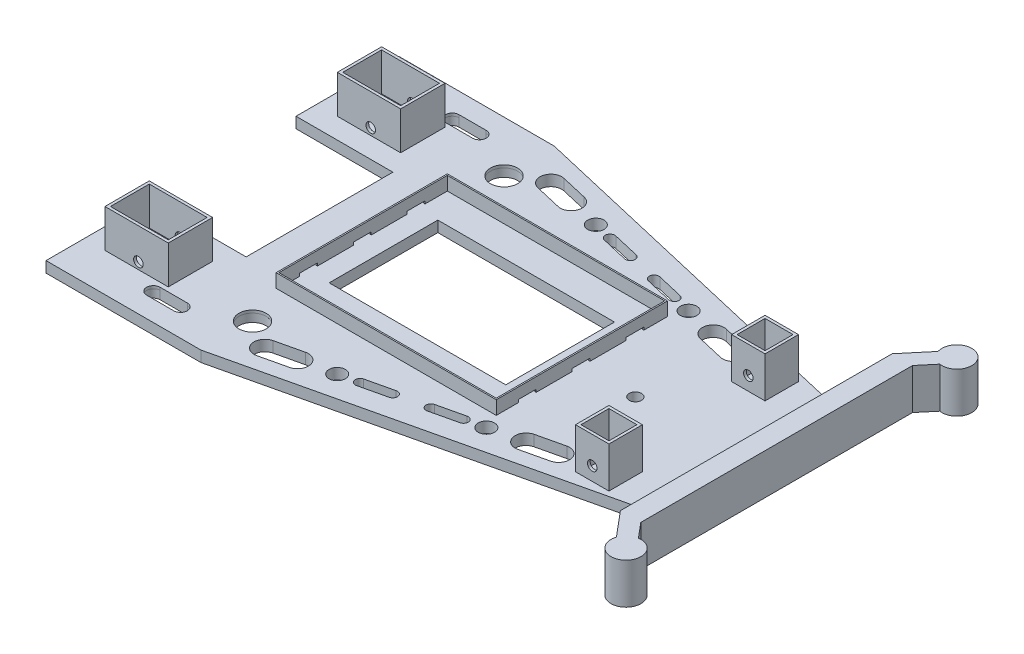
SolidWorks part; units mm, degrees
other "Markup1"
sketch "Sketch21" plane through (-125.0066, 16, 66.3806) normal (-0.0295, 0.9995, 0.0098) x (0.1853, -0.0042, 0.9827)
ref_plane "Front Plane" through (0, 0, 0) normal (0, 0, 1) x (1, 0, 0)
ref_plane "Top Plane" through (0, 0, 0) normal (0, 1, 0) x (1, 0, 0)
ref_plane "Right Plane" through (0, 0, 0) normal (1, 0, 0) x (0, 0, -1)
sketch "Sketch1" plane through (0, 0, 0) normal (0, 1, 0) x (1, 0, 0)
  line L0 (-125, -100) -> (-125, -65)
  line L1 (-125, -100) -> (125, -100)
  line L2 (-125, -100) -> (-125, 100)
  line L3 (-125, 100) -> (125, 100)
  line L4 (125, -100) -> (125, 100)
  line L5 (-125, -100) -> (125, 100) construction
  line L6 (-125, 100) -> (125, -100) construction
  line L7 (-125, -65) -> (-55, -65)
  line L8 (-55, -65) -> (-55, -100)
  line L9 (-55, -100) -> (-125, -100)
  line L10 (43.75, -65) -> (125, 0)
  line L11 (-55, 100) -> (-125, 100)
  line L12 (-55, 65) -> (-55, 100)
  line L13 (-125, 65) -> (-55, 65)
  line L14 (-125, 100) -> (-125, 65)
  line L15 (125, 0) -> (43.75, 65)
  line L16 (-55, -65) -> (43.75, -65)
  line L17 (-55, 65) -> (43.75, 65)
  line L18 (-131.3472, 0) -> (-131.3472, 27)
  line L19 (-131.3472, 27) -> (-76.3472, 27)
  line L20 (-76.3472, 27) -> (-76.3472, -27)
  line L21 (-76.3472, -27) -> (-131.5339, -27)
  line L22 (-131.3472, 0) -> (-131.3472, -27)
  line L29 (-82.5, 55) -> (-72.5, 55) construction
  line L31 (-82.5, -55) -> (-72.5, -55) construction
  line L32 (-82.5, -52.5) -> (-72.5, -52.5)
  line L33 (-82.5, -57.5) -> (-72.5, -57.5)
  line L34 (-82.5, 52.5) -> (-72.5, 52.5)
  line L35 (-82.5, 57.5) -> (-72.5, 57.5)
  arc A4 (-82.5, -52.5) -> (-82.5, -57.5) centre (-82.5, -55) ccw
  arc A5 (-72.5, -57.5) -> (-72.5, -52.5) centre (-72.5, -55) ccw
  circle A6 centre (-54.7227, -46.2677) radius 5
  circle A7 centre (-54.7227, 46.2677) radius 5
  arc A8 (-82.5, 52.5) -> (-82.5, 57.5) centre (-82.5, 55) cw
  arc A9 (-72.5, 57.5) -> (-72.5, 52.5) centre (-72.5, 55) cw
  point P0 (0, 0)
  point P44 (-77.5, -55)
  point P53 (-77.5, 55)
  dimension "D3" = 10
  dimension "D4" = 2.5
  dimension "D1" = 125
  dimension "D2" = 100
  dimension "D5" = 43.75
  dimension "D6" = 55
  dimension "D7" = 72.5
  dimension "D8" = 76.3472
  dimension "D9" = 77.5
  dimension "D10" = 27
  dimension "D11" = 131.3472
  dimension "D12" = 131.5339
  dimension "D13" = 46.2677
  dimension "D14" = 55
  dimension "D15" = 65
  dimension "D17" = 55
extrude "Boss-Extrude1" add sketch "Sketch1" along normal blind 1 contours L17 L13 L2 L7 L16 L10 L15 region at (-9.6002, 0, 0)
sketch "Sketch2" plane through (0, 0, 0) normal (0, 1, 0) x (1, 0, 0)
  line L1 (125, 0) -> (43.75, 65) construction
  line L2 (84.375, 32.5) -> (84.375, -32.5)
  line L3 (43.75, -65) -> (125, 0) construction
  line L4 (84.375, -32.5) -> (125, 0)
  line L5 (125, 0) -> (84.375, 32.5)
extrude "Cut-Extrude2" cut sketch "Sketch2" along normal through all both and the other way through all
sketch "Sketch3" plane through (0, 0, 0) normal (0, 1, 0) x (1, 0, 0)
  line L0 (84.375, -32.5) -> (-55, -65)
  line L1 (43.75, -65) -> (125, 0) construction
  line L2 (84.375, 32.5) -> (-55, 65)
  line L3 (125, 0) -> (43.75, 65) construction
  line L4 (-55, 65) -> (84.375, 65)
  line L5 (84.375, 65) -> (84.375, 32.5)
  line L6 (-55, -65) -> (84.375, -65)
  line L7 (84.375, -65) -> (84.375, -32.5)
extrude "Cut-Extrude4" cut sketch "Sketch3" along normal blind 1
sketch "Sketch8" plane through (0, 0, 0) normal (0, 1, 0) x (1, 0, 0)
  line L0 (-8.25, 0) -> (8.25, 0) construction
  line L2 (-103.4, 49.9) -> (-103.4, 35.6)
  line L3 (-103.4, 35.6) -> (-82.1, 35.6)
  line L5 (-103.4, 49.9) -> (-82.1, 35.6) construction
  line L6 (-103.4, 35.6) -> (-92.75, 42.75) construction
  line L7 (-103.4, -35.6) -> (-82.1, -49.9) construction
  line L8 (-103.4, -49.9) -> (-82.1, -35.6) construction
  line L9 (-82.1, -49.9) -> (-82.1, -35.6)
  line L10 (-103.4, -35.6) -> (-82.1, -35.6)
  line L11 (-103.4, -49.9) -> (-103.4, -35.6)
  line L12 (-103.4, -49.9) -> (-82.1, -49.9)
  line L13 (-92.75, 42.75) -> (-82.1, 49.9) construction
  line L15 (-103.4, 49.9) -> (-82.1, 49.9)
  line L16 (-82.1, 49.9) -> (-82.1, 35.6)
  point P4 (-98.075, 39.175)
  point P11 (-92.75, -42.75)
  point P12 (-99.75, 49.9)
  point P13 (-89.1, 49.9)
  dimension "D1" = 82.1
  dimension "D2" = 92.75
  dimension "D3" = 35.6
  dimension "D4" = 99.75
ref_plane "Plane1" through (0, 1, 0) normal (0, 1, 0) x (1, 0, 0)
sketch "Sketch9" plane through (0, 1, 0) normal (0, 1, 0) x (1, 0, 0)
  line L5 (-60.3125, -31) -> (19.6875, -31)
  line L6 (-60.3125, -31) -> (-60.3125, 31)
  line L7 (-60.3125, 31) -> (19.6875, 31)
  line L8 (19.6875, -31) -> (19.6875, 31)
  line L9 (-60.3125, -31) -> (19.6875, 31) construction
  line L10 (-60.3125, 31) -> (19.6875, -31) construction
  dimension "D1" = 19.6875
  dimension "D2" = 60.3125
  dimension "D3" = 31
  dimension "D4" = 31
extrude "Extrude-Thin1" add sketch "Sketch9" along normal blind 5 thin thin type one direction wall 0.5
sketch "Sketch10" plane through (0, 1, 0) normal (0, 1, 0) x (1, 0, 0)
  line L0 (19.6875, -31) -> (19.6875, 31) construction
  line L1 (19.6875, 31) -> (-60.3125, 31) construction
  line L3 (-57.4123, -23.4007) -> (-63.9346, -23.4007)
  line L4 (-57.4123, -23.4007) -> (-57.4123, -16.8007)
  line L5 (-57.4123, -16.8007) -> (-63.9346, -16.8007)
  line L6 (-63.9346, -23.4007) -> (-63.9346, -16.8007)
  line L8 (20.8822, 16.1993) -> (20.8822, 22.7993)
  line L9 (-59.5644, -3.6007) -> (-61.6509, -3.6007)
  line L10 (-59.5644, -3.6007) -> (-59.5644, 2.9993)
  line L11 (-59.5644, 2.9993) -> (-61.6509, 2.9993)
  line L12 (-61.6509, -3.6007) -> (-61.6509, 2.9993)
  line L14 (18.9394, 22.7993) -> (20.8822, 22.7993)
  line L15 (-59.5644, 16.1993) -> (-61.5072, 16.1993)
  line L16 (-59.5644, 16.1993) -> (-59.5644, 22.7993)
  line L17 (-59.5644, 22.7993) -> (-61.5072, 22.7993)
  line L18 (-61.5072, 16.1993) -> (-61.5072, 22.7993)
  line L19 (18.9394, 16.1993) -> (18.9394, 22.7993)
  line L20 (18.9394, 16.1993) -> (20.8822, 16.1993)
  line L21 (21.0259, -3.6007) -> (21.0259, 2.9993)
  line L22 (18.9394, 2.9993) -> (21.0259, 2.9993)
  line L23 (18.9394, -3.6007) -> (18.9394, 2.9993)
  line L24 (18.9394, -3.6007) -> (21.0259, -3.6007)
  line L25 (23.3096, -23.4007) -> (23.3096, -16.8007)
  line L26 (16.7873, -16.8007) -> (23.3096, -16.8007)
  line L27 (16.7873, -23.4007) -> (16.7873, -16.8007)
  line L28 (16.7873, -23.4007) -> (23.3096, -23.4007)
  dimension "D1" = 1.1947
  dimension "D2" = 1.3384
  dimension "D3" = 3.6221
  dimension "D4" = 0.7481
  dimension "D5" = 2.9002
  dimension "D6" = 77.0998
  dimension "D7" = 79.2519
  dimension "D8" = 8.2007
  dimension "D9" = 14.8007
  dimension "D10" = 28.0007
  dimension "D11" = 47.8007
extrude "Cut-Extrude10" cut sketch "Sketch10" along normal blind 1
sketch "Sketch11" plane through (0, 1, 0) normal (0, 1, 0) x (1, 0, 0)
  line L0 (-9.9, 0) -> (9.9, 0) construction
  line L5 (53.725, 23.5731) -> (64.025, 33.8731) construction
  line L6 (53.725, 33.8731) -> (64.025, 23.5731) construction
  line L8 (53.725, -33.8731) -> (64.025, -33.8731)
  line L13 (53.725, -33.8731) -> (53.725, -23.5731)
  line L18 (53.725, -23.5731) -> (64.025, -23.5731)
  line L19 (64.025, -33.8731) -> (64.025, -23.5731)
  line L20 (53.725, -33.8731) -> (64.025, -23.5731) construction
  line L21 (53.725, -23.5731) -> (64.025, -33.8731) construction
  line L22 (64.025, 33.8731) -> (64.025, 23.5731)
  line L23 (53.725, 23.5731) -> (64.025, 23.5731)
  line L24 (53.725, 33.8731) -> (53.725, 23.5731)
  line L25 (53.725, 33.8731) -> (64.025, 33.8731)
  point P6 (58.875, 28.7231)
  point P7 (58.875, -28.7231)
  point P12 (58.875, -28.7231)
  dimension "D1" = 53.725
  dimension "D2" = 58.875
  dimension "D3" = 23.5731
sketch "Sketch12" plane through (0, 1, 0) normal (0, 1, 0) x (1, 0, 0)
  line L0 (-43.8236, -52.6197) -> (-34.085, -50.3481) construction
  line L1 (-44.7322, -48.7243) -> (-34.9936, -46.4526)
  line L2 (-42.9149, -56.5151) -> (-33.1764, -54.2435)
  line L3 (15.4341, -38.7973) -> (5.6956, -41.0689) construction
  line L4 (15.0366, -37.093) -> (5.298, -39.3646)
  line L5 (-15.4341, -45.9976) -> (-5.6956, -43.726) construction
  line L6 (-15.8317, -44.2933) -> (-6.0931, -42.0217)
  line L7 (-15.0366, -47.7018) -> (-5.298, -45.4302)
  line L8 (15.8317, -40.5015) -> (6.0931, -42.7731)
  line L9 (43.8236, -32.1752) -> (34.085, -34.4468) construction
  line L10 (42.9149, -28.2797) -> (33.1764, -30.5514)
  line L11 (44.7322, -36.0706) -> (34.9936, -38.3422)
  line L12 (43.8236, 32.1752) -> (34.085, 34.4468) construction
  line L13 (42.9149, 28.2797) -> (33.1764, 30.5514)
  line L14 (44.7322, 36.0706) -> (34.9936, 38.3422)
  line L15 (15.4341, 38.7973) -> (5.6956, 41.0689) construction
  line L16 (15.0366, 37.093) -> (5.298, 39.3646)
  line L17 (15.8317, 40.5015) -> (6.0931, 42.7731)
  line L18 (-15.4341, 45.9976) -> (-5.6956, 43.726) construction
  line L19 (-15.8317, 44.2933) -> (-6.0931, 42.0217)
  line L20 (-15.0366, 47.7018) -> (-5.298, 45.4302)
  line L21 (-43.8236, 52.6197) -> (-34.085, 50.3481) construction
  line L22 (-44.7322, 48.7243) -> (-34.9936, 46.4526)
  line L23 (-42.9149, 56.5151) -> (-33.1764, 54.2435)
  arc A0 (-44.7322, -48.7243) -> (-42.9149, -56.5151) centre (-43.8236, -52.6197) ccw
  arc A1 (-33.1764, -54.2435) -> (-34.9936, -46.4526) centre (-34.085, -50.3481) ccw
  circle A2 centre (-22.2511, -47.5877) radius 3
  arc A3 (-15.8317, -44.2933) -> (-15.0366, -47.7018) centre (-15.4341, -45.9976) ccw
  arc A4 (-5.298, -45.4302) -> (-6.0931, -42.0217) centre (-5.6956, -43.726) ccw
  circle A5 centre (22.2511, -37.2071) radius 3
  arc A6 (15.0366, -37.093) -> (15.8317, -40.5015) centre (15.4341, -38.7973) cw
  arc A7 (6.0931, -42.7731) -> (5.298, -39.3646) centre (5.6956, -41.0689) cw
  arc A8 (42.9149, -28.2797) -> (44.7322, -36.0706) centre (43.8236, -32.1752) cw
  arc A9 (34.9936, -38.3422) -> (33.1764, -30.5514) centre (34.085, -34.4468) cw
  circle A10 centre (22.2511, 37.2071) radius 3
  circle A11 centre (-22.2511, 47.5877) radius 3
  arc A12 (42.9149, 28.2797) -> (44.7322, 36.0706) centre (43.8236, 32.1752) ccw
  arc A13 (34.9936, 38.3422) -> (33.1764, 30.5514) centre (34.085, 34.4468) ccw
  arc A14 (15.0366, 37.093) -> (15.8317, 40.5015) centre (15.4341, 38.7973) ccw
  arc A15 (6.0931, 42.7731) -> (5.298, 39.3646) centre (5.6956, 41.0689) ccw
  arc A16 (-15.8317, 44.2933) -> (-15.0366, 47.7018) centre (-15.4341, 45.9976) cw
  arc A17 (-5.298, 45.4302) -> (-6.0931, 42.0217) centre (-5.6956, 43.726) cw
  arc A18 (-44.7322, 48.7243) -> (-42.9149, 56.5151) centre (-43.8236, 52.6197) cw
  arc A19 (-33.1764, 54.2435) -> (-34.9936, 46.4526) centre (-34.085, 50.3481) cw
  point P0 (-38.9543, -51.4839)
  point P15 (-10.5649, -44.8618)
  point P21 (10.5649, -39.9331)
  point P27 (38.9543, -33.311)
  point P38 (38.9543, 33.311)
  point P45 (10.5649, 39.9331)
  point P52 (-10.5649, 44.8618)
  point P59 (-38.9543, 51.4839)
  dimension "D1" = 6
  dimension "D2" = 4
  dimension "D3" = 1.75
  dimension "D12" = 6
  dimension "D13" = 1.75
  dimension "D14" = 4
  dimension "D21" = 6
  dimension "D22" = 4
  dimension "D30" = 1.75
  dimension "D4" = 5.298
  dimension "D5" = 5.6956
  dimension "D6" = 10.5649
  dimension "D7" = 33.1764
  dimension "D8" = 5.298
  dimension "D9" = 33.1764
  dimension "D10" = 30.5514
  dimension "D11" = 22.2511
  dimension "D15" = 37.2071
  dimension "D16" = 5.298
  dimension "D17" = 5.6956
  dimension "D18" = 10.5649
  dimension "D19" = 33.1764
  dimension "D20" = 42.0217
  dimension "D23" = 22.2511
  dimension "D24" = 22.2511
  dimension "D25" = 22.2511
  dimension "D26" = 33.1764
  dimension "D27" = 38.9543
  dimension "D28" = 28.2797
  dimension "D29" = 47.5877
  dimension "D31" = 47.5877
  dimension "D32" = 5.298
  dimension "D33" = 10.5649
  dimension "D34" = 37.093
  dimension "D36" = 37.2071
extrude "Cut-Extrude12" cut sketch "Sketch12" against normal blind 10
ref_plane "Plane2" through (0, 1, 0) normal (0, 1, 0) x (1, 0, 0)
ref_plane "Plane3" through (0, 0, 0) normal (0, -1, 0) x (-1, 0, 0)
sketch "Sketch13" plane through (0, 0, 0) normal (0, -1, 0) x (-1, 0, 0)
  line L0 (125.0066, 100) -> (125.0066, 65)
  line L1 (125.0066, 100) -> (-124.9934, 100)
  line L2 (125.0066, 100) -> (125.0066, -100)
  line L3 (125.0066, -100) -> (-124.9934, -100)
  line L4 (-124.9934, 100) -> (-124.9934, -100)
  line L5 (125.0066, 100) -> (-124.9934, -100) construction
  line L6 (125.0066, -100) -> (-124.9934, 100) construction
  line L7 (125.0066, 65) -> (55.0066, 65)
  line L8 (55.0066, 65) -> (55.0066, 100)
  line L9 (55.0066, 100) -> (125.0066, 100)
  line L10 (-43.7434, 65) -> (-124.9934, 0)
  line L11 (55.0066, -100) -> (125.0066, -100)
  line L12 (55.0066, -65) -> (55.0066, -100)
  line L13 (125.0066, -65) -> (55.0066, -65)
  line L14 (125.0066, -100) -> (125.0066, -65)
  line L15 (-124.9934, 0) -> (-43.7434, -65)
  line L16 (55.0066, 65) -> (-43.7434, 65)
  line L17 (55.0066, -65) -> (-43.7434, -65)
  line L18 (131.3538, 0) -> (131.3538, -27)
  line L19 (131.3538, -27) -> (76.3538, -27)
  line L20 (76.3538, -27) -> (76.3538, 27)
  line L21 (76.3538, 27) -> (131.5405, 27)
  line L22 (131.3538, 0) -> (131.3538, 27)
  line L26 (82.5066, -55) -> (72.5066, -55) construction
  line L27 (82.5066, 55) -> (72.5066, 55) construction
  line L28 (82.5066, 52.5) -> (72.5066, 52.5)
  line L29 (82.5066, 57.5) -> (72.5066, 57.5)
  line L30 (82.5066, -52.5) -> (72.5066, -52.5)
  line L31 (82.5066, -57.5) -> (72.5066, -57.5)
  arc A4 (82.5066, 52.5) -> (82.5066, 57.5) centre (82.5066, 55) ccw
  arc A5 (72.5066, 57.5) -> (72.5066, 52.5) centre (72.5066, 55) ccw
  circle A6 centre (54.7293, 46.2677) radius 5
  circle A7 centre (54.7293, -46.2677) radius 5
  arc A8 (82.5066, -52.5) -> (82.5066, -57.5) centre (82.5066, -55) cw
  arc A9 (72.5066, -57.5) -> (72.5066, -52.5) centre (72.5066, -55) cw
  point P0 (0.0066, 0)
  point P36 (77.5066, 55)
  point P44 (77.5066, -55)
  dimension "D1" = 10
  dimension "D2" = 2.5
  dimension "D3" = 0.0066
  dimension "D4" = 54.7293
  dimension "D5" = 55.0066
  dimension "D6" = 72.5066
  dimension "D7" = 76.3538
  dimension "D8" = 77.5066
  dimension "D9" = 125.0066
  dimension "D10" = 27
  dimension "D11" = 131.3538
  dimension "D12" = 131.5405
  dimension "D13" = 43.7434
  dimension "D14" = 46.2677
  dimension "D15" = 55
  dimension "D16" = 65
  dimension "D17" = 100
  dimension "D19" = 46.2677
  dimension "D20" = 55
extrude "Boss-Extrude2" add sketch "Sketch13" along normal blind 3 contours L20 L21 L2 L7 L16 L10 L15 L17 L13 L19 L31 A9 L30 A8 A7 A6 A5 L29 A4 L28 region at (-9.6068, 0, 0)
sketch "Sketch14" plane through (0, 0, 0) normal (0, 1, 0) x (1, 0, 0)
  line L0 (-55, 65) -> (43.7434, 65)
  line L1 (-55, 65) -> (84.375, 32.5) construction
  line L2 (-55, 65) -> (43.7434, 65) construction
  line L3 (43.7434, 65) -> (84.375, 32.4947)
  line L4 (84.375, -32.4947) -> (84.375, 32.4947) construction
  line L5 (84.375, 32.5) -> (84.375, -32.5) construction
  line L6 (84.375, 32.4947) -> (-55, 65)
  line L7 (84.375, 32.4947) -> (84.3657, -32.5022)
  line L8 (84.3657, -32.5022) -> (124.9934, 0)
  line L9 (124.9934, 0) -> (84.375, -32.4947) construction
  line L10 (84.375, 32.4947) -> (124.9934, 0) construction
  line L11 (124.9934, 0) -> (84.375, 32.4947)
  line L12 (84.3657, -32.5022) -> (-55, -65)
  line L13 (-55, -65) -> (43.7434, -65)
  line L14 (43.7434, -65) -> (84.3657, -32.5022)
  line M1 (84.375, 32.4947) -> (84.375, -32.4947)
  line M2 (84.375, -32.4947) -> (124.9934, 0)
  line M3 (124.9934, 0) -> (84.375, 32.4947)
extrude "Cut-Extrude13" cut sketch "Sketch14" against normal blind 43 contours L6 L3 L0 | M3 M1 M2 | L13 L14 L12 region at (24.3697, 0, 54.1674) region at (97.9145, 0, 0) region at (24.3728, 0, -54.1649)
sketch "Sketch15" plane through (0, 1, 0) normal (0, 1, 0) x (1, 0, 0)
  line L0 (-43.8236, -52.6197) -> (-34.085, -50.3481) construction
  line L1 (-44.7322, -48.7243) -> (-34.9936, -46.4526)
  line L2 (-42.9149, -56.5151) -> (-33.1764, -54.2435)
  line L3 (-15.4341, -45.9976) -> (-5.6956, -43.726) construction
  line L4 (-15.8317, -44.2933) -> (-6.0931, -42.0217)
  line L5 (-15.0366, -47.7018) -> (-5.298, -45.4302)
  line L6 (5.6956, -41.0689) -> (15.4341, -38.7973) construction
  line L7 (5.298, -39.3646) -> (15.0366, -37.093)
  line L8 (6.0931, -42.7731) -> (15.8317, -40.5015)
  line L9 (34.085, -34.4468) -> (43.8236, -32.1752) construction
  line L10 (33.1764, -30.5514) -> (42.9149, -28.2797)
  line L11 (34.9936, -38.3422) -> (44.7322, -36.0706)
  line L12 (84.375, 0) -> (-91.8075, 0)
  line L13 (84.375, 32.5) -> (84.375, -32.5) construction
  line L14 (34.085, 34.4468) -> (43.8236, 32.1752) construction
  line L15 (33.1764, 30.5514) -> (42.9149, 28.2797)
  line L16 (34.9936, 38.3422) -> (44.7322, 36.0706)
  line L17 (5.6956, 41.0689) -> (15.4341, 38.7973) construction
  line L18 (5.298, 39.3646) -> (15.0366, 37.093)
  line L19 (6.0931, 42.7731) -> (15.8317, 40.5015)
  line L20 (-15.4341, 45.9976) -> (-5.6956, 43.726) construction
  line L21 (-15.8317, 44.2933) -> (-6.0931, 42.0217)
  line L22 (-15.0366, 47.7018) -> (-5.298, 45.4302)
  line L23 (-43.8236, 52.6197) -> (-34.085, 50.3481) construction
  line L24 (-44.7322, 48.7243) -> (-34.9936, 46.4526)
  line L25 (-42.9149, 56.5151) -> (-33.1764, 54.2435)
  line L26 (-60.8125, -23.4007) -> (-60.8125, -31.5) construction
  arc A0 (-44.7322, -48.7243) -> (-42.9149, -56.5151) centre (-43.8236, -52.6197) ccw
  arc A1 (-33.1764, -54.2435) -> (-34.9936, -46.4526) centre (-34.085, -50.3481) ccw
  arc A2 (-15.8317, -44.2933) -> (-15.0366, -47.7018) centre (-15.4341, -45.9976) ccw
  arc A3 (-5.298, -45.4302) -> (-6.0931, -42.0217) centre (-5.6956, -43.726) ccw
  arc A4 (5.298, -39.3646) -> (6.0931, -42.7731) centre (5.6956, -41.0689) ccw
  arc A5 (15.8317, -40.5015) -> (15.0366, -37.093) centre (15.4341, -38.7973) ccw
  arc A6 (33.1764, -30.5514) -> (34.9936, -38.3422) centre (34.085, -34.4468) ccw
  arc A7 (44.7322, -36.0706) -> (42.9149, -28.2797) centre (43.8236, -32.1752) ccw
  circle A8 centre (-22.2511, -47.5877) radius 3
  circle A9 centre (22.2511, -37.2071) radius 3
  circle A12 centre (22.2511, 37.2071) radius 3
  circle A13 centre (-22.2511, 47.5877) radius 3
  arc A14 (33.1764, 30.5514) -> (34.9936, 38.3422) centre (34.085, 34.4468) cw
  arc A15 (44.7322, 36.0706) -> (42.9149, 28.2797) centre (43.8236, 32.1752) cw
  arc A16 (5.298, 39.3646) -> (6.0931, 42.7731) centre (5.6956, 41.0689) cw
  arc A17 (15.8317, 40.5015) -> (15.0366, 37.093) centre (15.4341, 38.7973) cw
  arc A18 (-15.8317, 44.2933) -> (-15.0366, 47.7018) centre (-15.4341, 45.9976) cw
  arc A19 (-5.298, 45.4302) -> (-6.0931, 42.0217) centre (-5.6956, 43.726) cw
  arc A20 (-44.7322, 48.7243) -> (-42.9149, 56.5151) centre (-43.8236, 52.6197) cw
  arc A21 (-33.1764, 54.2435) -> (-34.9936, 46.4526) centre (-34.085, 50.3481) cw
  point P4 (-38.9543, -51.4839)
  point P9 (-10.5649, -44.8618)
  point P18 (10.5649, -39.9331)
  point P27 (38.9543, -33.311)
  point P58 (38.9543, 33.311)
  point P65 (10.5649, 39.9331)
  point P72 (-10.5649, 44.8618)
  point P79 (-38.9543, 51.4839)
  dimension "D1" = 6
  dimension "D2" = 4
  dimension "D3" = 1.75
  dimension "D4" = 30.995
extrude "Cut-Extrude14" cut sketch "Sketch15" against normal blind 38 contours L2 A1 L1 A0 | A8 | L5 A3 L4 A2 | L8 A5 L7 A4 | A9 | L11 A7 L10 A6 | A15 L16 A14 L15 | A12 | A17 L19 A16 L18 | A19 L22 A18 L21 | A13 | A21 L25 A20 L24 region at (-38.9543, 1, 51.4839) region at (-10.5649, 1, 44.8618) region at (10.5649, 1, 39.9331) region at (38.9543, 1, 33.311) region at (38.9543, 1, -33.311) region at (10.5649, 1, -39.9331) region at (-10.5649, 1, -44.8618) region at (-38.9543, 1, -51.4839) region at (-22.2511, 1, 47.5877) region at (22.2511, 1, 37.2071) region at (22.2511, 1, -37.2071) region at (-22.2511, 1, -47.5877)
ref_plane "Plane4" through (0, -3, 0) normal (0, -1, 0) x (-1, 0, 0)
sketch "Sketch17" plane through (0, -3, 0) normal (0, -1, 0) x (-1, 0, 0)
  line L0 (-84.375, 50) -> (-84.375, -50)
  line L1 (-84.375, -50) -> (-91.875, -50)
  line L2 (-91.875, -50) -> (-91.875, 50)
  line L3 (-91.875, 50) -> (-84.375, 50)
  line L4 (-91.875, 50) -> (-96.4474, 55.4492)
  line L5 (-84.375, 50) -> (-92.0816, 59.1844)
  line L6 (-91.875, -50) -> (-96.4474, -55.4492)
  line L7 (-84.375, -50) -> (-92.0816, -59.1844)
  arc A0 (-92.0816, 59.1844) -> (-96.4474, 55.4492) centre (-97.3135, 60.8806) ccw
  arc A1 (-92.0816, -59.1844) -> (-96.4474, -55.4492) centre (-97.3135, -60.8806) cw
  point P4 (-84.375, 0)
  point P11 (-84.375, 0)
  dimension "D2" = 5.5
  dimension "D1" = 100
  dimension "D3" = 84.375
  dimension "D4" = 91.875
  dimension "D5" = 92.0816
  dimension "D6" = 96.4474
  dimension "D7" = 97.3135
extrude "Boss-Extrude3" add sketch "Sketch17" against normal blind 15 contours L3 L2 L1 L0 | L5 A0 L4 L3 | A1 L7 L1 L6 region at (88.125, -3, 0) region at (95.0012, -3, -58.2916) region at (95.0012, -3, 58.2916)
sketch "Sketch18" plane through (0, 1, 0) normal (0, 1, 0) x (1, 0, 0)
  line L0 (84.375, -32.5) -> (84.375, -16.25)
  line L1 (84.375, 50) -> (84.375, -50) construction
  line L2 (84.375, -16.25) -> (73.375, -16.25)
  line L3 (-60.8125, -23.4007) -> (-60.8125, -31.5) construction
  line L4 (-60.8125, -31.5) -> (20.1875, -31.5) construction
  dimension "D1" = 134.1875
  dimension "D2" = 15.25
sketch "Sketch19" plane through (84.375, 0, 0) normal (-1, 0, 0) x (0, 0, 1)
  line L0 (16.25, 1) -> (16.25, 12)
  line L1 (-50, 12) -> (50, 12) construction
ref_plane "Plane5" through (0, 0, 16.25) normal (0, 0, 1) x (1, 0, 0)
sketch "Sketch20" plane through (0, 0, 16.25) normal (0, 0, 1) x (1, 0, 0)
  line L0 (73.375, 1) -> (84.375, 12)
  line L1 (84.375, 1) -> (73.375, 1) construction
  dimension "D1" = 73.375
rib "Rib2" sketch "Sketch20" sketch "Sketch20" thickness 5 extrusion direction parallel to sketch draft on no parameters "D1"=5
mirror "Mirror1" about plane through (0, 0, 0) normal (0, 0, 1) of "Rib2"
extrude "Extrude-Thin2" add sketch "Sketch8" along normal blind 15 thin thin type one direction wall 1
extrude "Extrude-Thin4" add sketch "Sketch11" along normal blind 15 thin thin type one direction wall 1
ref_plane "Plane7" through (0, 0, 34.8731) normal (0, 0, 1) x (1, 0, 0)
ref_plane "Plane6" through (0, 0, 50.9) normal (0, 0, 1) x (1, 0, 0)
sketch "Sketch22" plane through (0, 0, 50.9) normal (0, 0, 1) x (1, 0, 0)
  line L0 (-92.1, 3.5) -> (-81.1, 3.5)
  line L2 (-81.1, 15) -> (-81.1, 1) construction
  circle A0 centre (-92.1, 3.5) radius 1.75
  dimension "D1" = 3.5
  dimension "D2" = 92.1
  dimension "D3" = 3.5
extrude "Cut-Extrude16" cut sketch "Sketch22" against normal blind 111 contours A0 region at (-93.8005, 3.5, 50.9)
sketch "Sketch27" plane through (0, 0, 34.8731) normal (0, 0, 1) x (1, 0, 0)
  line L0 (65.025, 1) -> (58.875, 1)
  line L1 (52.725, 1) -> (65.025, 1) construction
  line L2 (58.875, 1) -> (58.875, 6)
  circle A0 centre (58.875, 6) radius 1.75
  dimension "D1" = 3.5
  dimension "D2" = 5
extrude "Cut-Extrude17" cut sketch "Sketch27" against normal blind 77 contours A0 region at (60.0774, 4.7976, 34.8731)
sketch "Sketch28" plane through (0, 1, 0) normal (0, 1, 0) x (1, 0, 0)
  line L0 (-125, 65) -> (-112, 65)
  line L1 (-125, 65) -> (-55, 65) construction
  line L2 (-125, 27) -> (-125, 65) construction
  line L3 (-112, 65) -> (-112, -65)
  line L4 (-125, -65) -> (-55, -65) construction
  line L5 (-112, -65) -> (-125, -65)
  line L7 (-125, 65) -> (-137.051, 65)
  line L8 (-137.051, 65) -> (-137.051, -65)
  line L9 (-137.051, -65) -> (-125, -65)
  line L11 (84.375, 13.75) -> (84.375, -13.75) construction
  dimension "D1" = 196.375
  dimension "D2" = 221.426
extrude "Cut-Extrude20" cut sketch "Sketch28" against normal blind 35
sketch "Sketch29" plane through (0, 1, 0) normal (0, 1, 0) x (1, 0, 0)
  line L1 (39.875, 0) -> (77.875, 0)
  line L2 (84.375, 13.75) -> (84.375, -13.75) construction
  circle A0 centre (77.875, 0) radius 2.25
  circle A1 centre (39.875, 0) radius 2.25
  point P1 (58.875, 0)
  point P4 (58.875, 0)
  point P8 (58.875, 0)
  dimension "D1" = 4.5
  dimension "D2" = 6.5
extrude "Cut-Extrude21" cut sketch "Sketch29" against normal blind 30 contours A0 | A1 region at (77.875, 1, -2.1864)
sketch "Sketch30" plane through (0, -3, 0) normal (0, -1, 0) x (1, 0, 0)
  line L0 (91.875, 0) -> (-20.3125, 0)
  line L1 (91.875, 50) -> (91.875, -50) construction
  line L2 (-112, -65) -> (-112, -27) construction
  line L3 (-52.8125, -20) -> (12.1875, -20)
  line L4 (-52.8125, -20) -> (-52.8125, 20)
  line L5 (-52.8125, 20) -> (12.1875, 20)
  line L6 (12.1875, -20) -> (12.1875, 20)
  line L7 (-52.8125, -20) -> (12.1875, 20) construction
  line L8 (-52.8125, 20) -> (12.1875, -20) construction
  line L9 (-76.3538, -27) -> (-112, -27) construction
  dimension "D1" = 59.1875
  dimension "D2" = 91.6875
  dimension "D3" = 7
extrude "Cut-Extrude22" cut sketch "Sketch30" against normal blind 10 contours L3 L6 L5 L4 region at (-52.0493, -3, 0)
